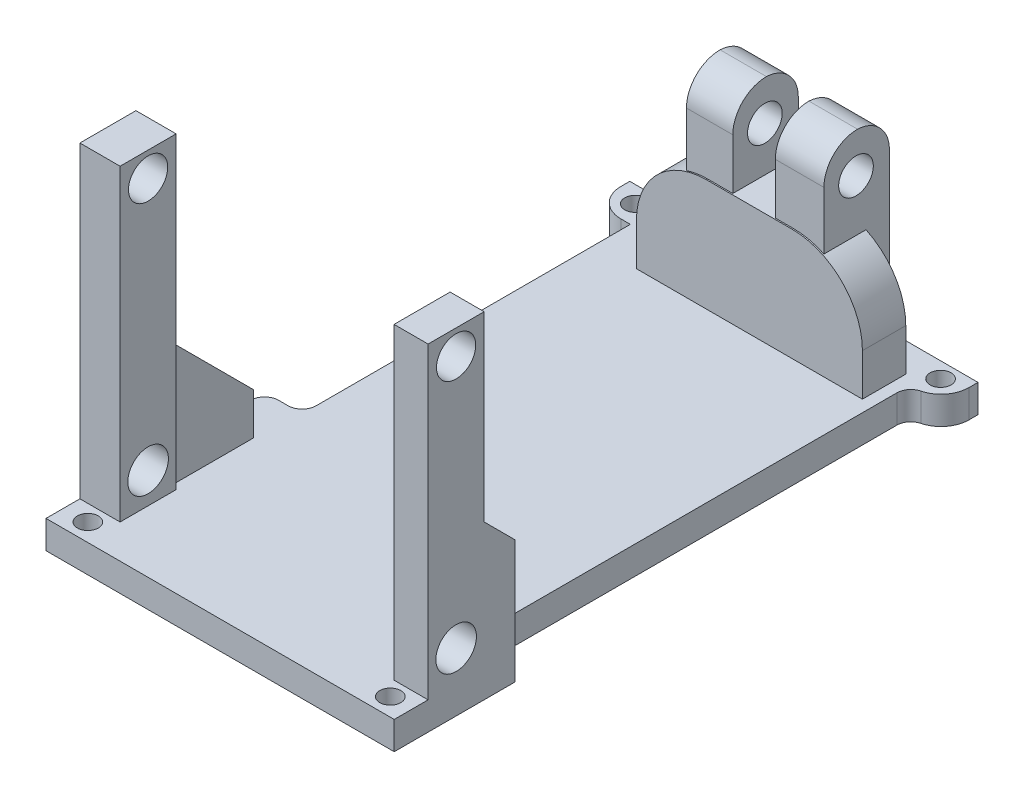
SolidWorks part; units mm, degrees
ref_plane "前视基准面" through (0, 0, 0) normal (0, 0, 1) x (1, 0, 0)
ref_plane "上视基准面" through (0, 0, 0) normal (0, 1, 0) x (1, 0, 0)
ref_plane "右视基准面" through (0, 0, 0) normal (1, 0, 0) x (0, 0, -1)
sketch "草图1" plane through (0, 0, 0) normal (0, 1, 0) x (1, 0, 0)
  line L0 (0, 20.84) -> (0, -28.4823) construction
  line L1 (12.43, -20.84) -> (-12.43, -20.84)
  line L2 (12.43, -20.84) -> (12.43, 20.84)
  line L3 (12.43, 20.84) -> (-12.43, 20.84)
  line L4 (-12.43, -20.84) -> (-12.43, 20.84)
  line L5 (12.43, -20.84) -> (-12.43, 20.84) construction
  line L6 (12.43, 20.84) -> (-12.43, -20.84) construction
  line L7 (0, -20.84) -> (0, -17.37) construction
  circle A0 centre (-10.8428, 19.643) radius 0.75
  circle A1 centre (10.8787, 19.7198) radius 0.75
  circle A2 centre (-10.7139, -19.5685) radius 0.75
  circle A3 centre (10.8787, -19.5685) radius 0.75
  point P0 (0, 0)
extrude "凸台-拉伸2" add sketch "草图1" along normal blind 2
sketch "草图4" plane through (0, 0, 0) normal (0, 1, 0) x (1, 0, 0)
  line L0 (0, 0) -> (0, 20.84) construction
  line L1 (12.43, 20.84) -> (-12.43, 20.84) construction
  line L2 (0, 0) -> (0, -20.84) construction
  line L3 (-12.43, -20.84) -> (12.43, -20.84) construction
  line L4 (-12.43, -20.84) -> (-12.43, -18.42) construction
  line L5 (-12.43, 20.84) -> (-12.43, -20.84) construction
  line L6 (12.43, -18.42) -> (27.1569, -18.42) construction
  line L7 (12.43, -20.84) -> (12.43, 20.84) construction
  line L8 (27.1569, -18.42) -> (30.8429, -18.42) construction
  line L9 (30.8429, -18.42) -> (-25.5307, -18.42) construction
  line L11 (-12.43, -18.42) -> (-9.5608, -18.42)
  line L12 (-12.43, -18.42) -> (-12.43, -14.4185)
  line L13 (-12.43, -14.4185) -> (-9.5608, -14.4185)
  line L14 (-9.5608, -18.42) -> (-9.5608, -14.4185)
  line L15 (12.43, -18.42) -> (10, -18.42)
  line L16 (12.43, -18.42) -> (12.43, -14.42)
  line L17 (12.43, -14.42) -> (10, -14.42)
  line L18 (10, -18.42) -> (10, -14.42)
extrude "凸台-拉伸3" add sketch "草图4" along normal blind 24
sketch "草图5" plane through (0, 0, 0) normal (1, 0, 0) x (0, 0, -1)
  line L0 (-18.42, 2) -> (-18.42, 2.75) construction
  line L1 (-18.42, 24) -> (-18.42, 2) construction
  line L2 (-18.42, 2.75) -> (-18.42, 5.65) construction
  line L4 (-18.42, 2) -> (-18.42, 4.2) construction
  circle A0 centre (-16.4193, 4.2) radius 1.45
sketch "草图8" plane through (0, 0, 0) normal (0, 1, 0) x (1, 0, 0)
  line L0 (0, 20.84) -> (0, 15.7644) construction
  line L1 (12.43, 20.84) -> (-12.43, 20.84) construction
  line L2 (-9.5608, -14.4185) -> (-9.5608, 21.9261) construction
  line L3 (10, -14.42) -> (10, 21.9261) construction
  line L4 (10, 15.7644) -> (6.5055, 15.7644) construction
  line L5 (-9.5608, 15.7644) -> (-3.3103, 15.7644) construction
  line L6 (-3.3103, 20.84) -> (-3.3103, 20.44) construction
  line L8 (-3.3103, 20.44) -> (0, 20.44)
  line L9 (-3.3103, 20.44) -> (-3.3103, 15.7644)
  line L10 (-3.3103, 15.7644) -> (0, 15.7644)
  line L11 (0, 20.44) -> (0, 15.7644)
  line L12 (6.5055, 15.7644) -> (3.0355, 15.7644)
  line L13 (6.5055, 15.7644) -> (6.5055, 20.44)
  line L14 (6.5055, 20.44) -> (3.0355, 20.44)
  line L15 (3.0355, 15.7644) -> (3.0355, 20.44)
extrude "凸台-拉伸5" add sketch "草图8" along normal blind 16.03
fillet "圆角5" radius 2.4 1 edges at (-1.6551, 16.03, -15.7644)
fillet "圆角6" radius 2.4 1 edges at (4.7705, 16.03, -15.7644)
fillet "圆角7" radius 2.4 1 edges at (4.7705, 16.03, -20.44)
fillet "圆角8" radius 2.4 1 edges at (-1.6551, 16.03, -20.44)
sketch "草图13" plane through (0, 0, 0) normal (1, 0, 0) x (0, 0, -1)
  circle A0 centre (18.0529, 13.1977) radius 1.2369
extrude "切除-拉伸7" cut sketch "草图13" against normal blind 16.03 and the other way blind 16.03
extrude "切除-拉伸8" cut sketch "草图5" against normal blind 16.03 and the other way blind 16.03
sketch "草图14" plane through (0, 0, 0) normal (1, 0, 0) x (0, 0, -1)
  circle A0 centre (-16.4193, 22.2411) radius 1.4
extrude "切除-拉伸9" cut sketch "草图14" against normal blind 16.03 and the other way blind 16.03
sketch "草图16" plane through (0, 0, 0) normal (0, 1, 0) x (1, 0, 0)
  line L1 (-6.791, 18.7702) -> (9.3444, 18.7702)
  line L2 (-6.791, 18.7702) -> (-6.791, 15.6735)
  line L3 (-6.791, 15.6735) -> (9.3444, 15.6735)
  line L4 (9.3444, 18.7702) -> (9.3444, 15.6735)
extrude "凸台-拉伸8" add sketch "草图16" along normal blind 10
fillet "圆角10" radius 5 1 edges at (-6.791, 10, -17.2219)
fillet "圆角13" radius 5 1 edges at (9.3444, 10, -17.2219)
sketch "草图17" plane through (0, 0, 0) normal (0, 1, 0) x (1, 0, 0)
  line L0 (-12.43, 20.84) -> (-12.43, -14.4185) construction
  line L1 (-12.43, -8.4724) -> (-9.9963, -8.4724)
  line L2 (-12.43, -8.4724) -> (-12.43, -14.4185)
  line L3 (-12.43, -14.4185) -> (-9.9963, -14.4185)
  line L4 (-9.9963, -8.4724) -> (-9.9963, -14.4185)
  line L5 (-9.5608, -14.4185) -> (-12.43, -14.4185) construction
  line L6 (10, -14.42) -> (12.43, -14.42) construction
  line L7 (10.8655, -14.42) -> (12.43, -14.42)
  line L8 (10.8655, -14.42) -> (10.8655, -8.42)
  line L9 (10.8655, -8.42) -> (12.43, -8.42)
  line L10 (12.43, -14.42) -> (12.43, -8.42)
  line L11 (12.43, -14.42) -> (12.43, 20.84) construction
extrude "凸台-拉伸9" add sketch "草图17" along normal blind 15
chamfer "倒角1" distance 10 angle 45 1 edges at (-11.2131, 15, 8.4724)
chamfer "倒角2" distance 10 angle 45 1 edges at (11.6478, 15, 8.42)
sketch "草图18" plane through (0, 0, 0) normal (0, 1, 0) x (1, 0, 0)
  line L0 (0, 20.84) -> (0, 18.2) construction
  line L1 (12.43, 20.84) -> (-12.43, 20.84) construction
  line L2 (0, 18.2) -> (12.43, 18.2) construction
  line L3 (12.43, -8.42) -> (12.43, 20.84) construction
  line L4 (12.43, 18.2) -> (10.181, 18.2) construction
  line L5 (-9.75, 18.2) -> (16.0992, 18.2) construction
  line L6 (10.181, 18.2) -> (12.43, 18.2)
  line L7 (10.181, 18.2) -> (10.181, -12.2103)
  line L8 (10.181, -12.2103) -> (12.43, -12.2103)
  line L9 (12.43, 18.2) -> (12.43, -12.2103)
sketch "草图19" plane through (0, 0, 0) normal (0, 1, 0) x (1, 0, 0)
  line L0 (-12.43, 20.84) -> (-12.43, 18.2) construction
  line L1 (-12.43, 20.84) -> (-12.43, -8.4724) construction
  line L2 (-12.43, 18.2) -> (-9.75, 18.2) construction
  line L3 (-9.75, 18.2) -> (-9.75, -5.2338) construction
  line L4 (-12.43, 20.84) -> (-12.43, -20.84) construction
  line L5 (-9.75, 18.2) -> (-12.43, 18.2)
  line L6 (-9.75, 18.2) -> (-9.75, -5.2338)
  line L7 (-9.75, -5.2338) -> (-12.43, -5.2338)
  line L8 (-12.43, 18.2) -> (-12.43, -5.2338)
  line L9 (-9.75, -5.2338) -> (12.9446, -5.2338) construction
sketch "草图20" plane through (0, 0, 0) normal (0, 1, 0) x (1, 0, 0)
  line L0 (-9.75, 18.2) -> (16.0992, 18.2) construction
extrude "切除-拉伸16" cut sketch "草图19" against normal blind 10 and the other way blind 10
extrude "切除-拉伸17" cut sketch "草图18" against normal blind 10 and the other way blind 10
fillet "圆角17" radius 2 1 edges at (12.43, 1, -18.2)
fillet "圆角18" radius 2 1 edges at (-12.43, 1, -18.2)
fillet "圆角19" radius 1 4 edges at (10.181, 1, -18.2) (10.181, 1, 12.2103) (-12.43, 1, 5.2338) (-9.75, 1, 5.2338)
